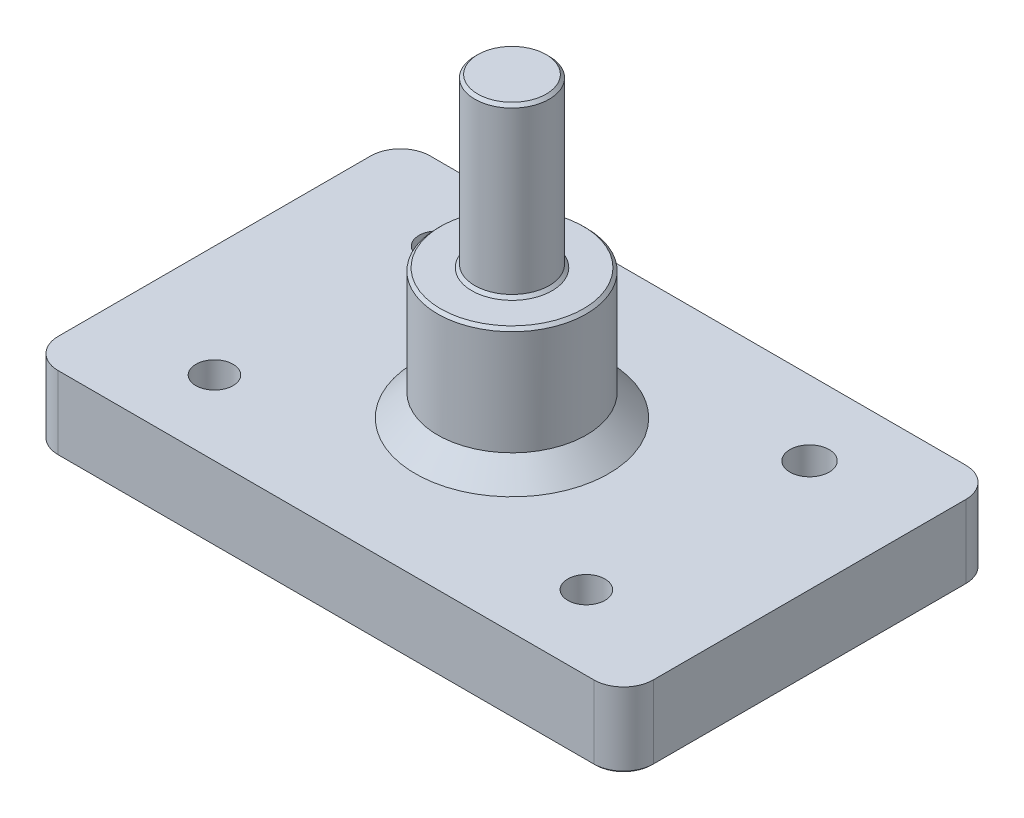
SolidWorks part; units mm, degrees
ref_plane "Front Plane" through (0, 0, 0) normal (0, 0, 1) x (1, 0, 0)
ref_plane "Top Plane" through (0, 0, 0) normal (0, 1, 0) x (1, 0, 0)
ref_plane "Right Plane" through (0, 0, 0) normal (1, 0, 0) x (0, 0, -1)
sketch "Sketch1" plane through (0, 0, 0) normal (0, 1, 0) x (1, 0, 0)
  line L0 (-31.75, 19.05) -> (-31.75, -19.05) construction
  line L1 (-50.8, -31.75) -> (50.8, -31.75)
  line L2 (-50.8, -31.75) -> (-50.8, 31.75)
  line L3 (-50.8, 31.75) -> (50.8, 31.75)
  line L4 (50.8, -31.75) -> (50.8, 31.75)
  line L5 (-50.8, -31.75) -> (50.8, 31.75) construction
  line L6 (-50.8, 31.75) -> (50.8, -31.75) construction
  line L7 (-31.75, -19.05) -> (31.75, -19.05) construction
  line L8 (31.75, -19.05) -> (31.75, 19.05) construction
  line L9 (31.75, 19.05) -> (-31.75, 19.05) construction
  line L10 (-31.75, 19.05) -> (31.75, -19.05) construction
  line L11 (31.75, 19.05) -> (-31.75, -19.05) construction
  circle A0 centre (-31.75, 19.05) radius 3.175
  circle A1 centre (-31.75, -19.05) radius 3.175
  circle A2 centre (31.75, -19.05) radius 3.175
  circle A3 centre (31.75, 19.05) radius 3.3492
  point P0 (0, 0)
  point P11 (0, 0)
  dimension "D3" = 6.35
  dimension "D1" = 63.5
  dimension "D2" = 101.6
  dimension "D4" = 63.5
  dimension "D5" = 38.1
extrude "Boss-Extrude1" add sketch "Sketch1" along normal blind 12.7
sketch "Sketch2" plane through (0, 12.7, 0) normal (0, 1, 0) x (1, 0, 0)
  circle A0 centre (0, 0) radius 12.7
  dimension "D1" = 25.4
extrude "Boss-Extrude2" add sketch "Sketch2" along normal blind 50.8
chamfer "Chamfer1" distance 3.81 angle 45 1 edges at (0, 12.7, 12.7)
fillet "Fillet1" radius 5.08 4 edges at (-50.8, 6.35, 31.75) (50.8, 6.35, 31.75) (50.8, 6.35, -31.75) (-50.8, 6.35, -31.75)
chamfer "Chamfer2" distance 0.254 angle 45 12 edges at (31.75, 0, -15.7008) (-31.75, 0, -15.875) (49.3121, 0, 30.2621) (50.8, 0, 0) (49.3121, 0, -30.2621) (0, 0, -31.75) (-49.3121, 0, -30.2621) (-50.8, 0, 0) (-49.3121, 0, 30.2621) (0, 0, 31.75) (-31.75, 0, 22.225) (31.75, 0, 22.225)
sketch "Sketch3" plane through (0, 63.5, 0) normal (0, 1, 0) x (1, 0, 0)
  circle A0 centre (0, 0) radius 12.7
  circle A1 centre (0, 0) radius 6.35
  dimension "D1" = 12.7
extrude "Cut-Extrude1" cut sketch "Sketch3" against normal blind 28.575
chamfer "Chamfer3" distance 0.508 angle 45 3 edges at (0, 63.5, 6.35) (0, 34.925, 12.7) (0, 34.925, 6.35)
